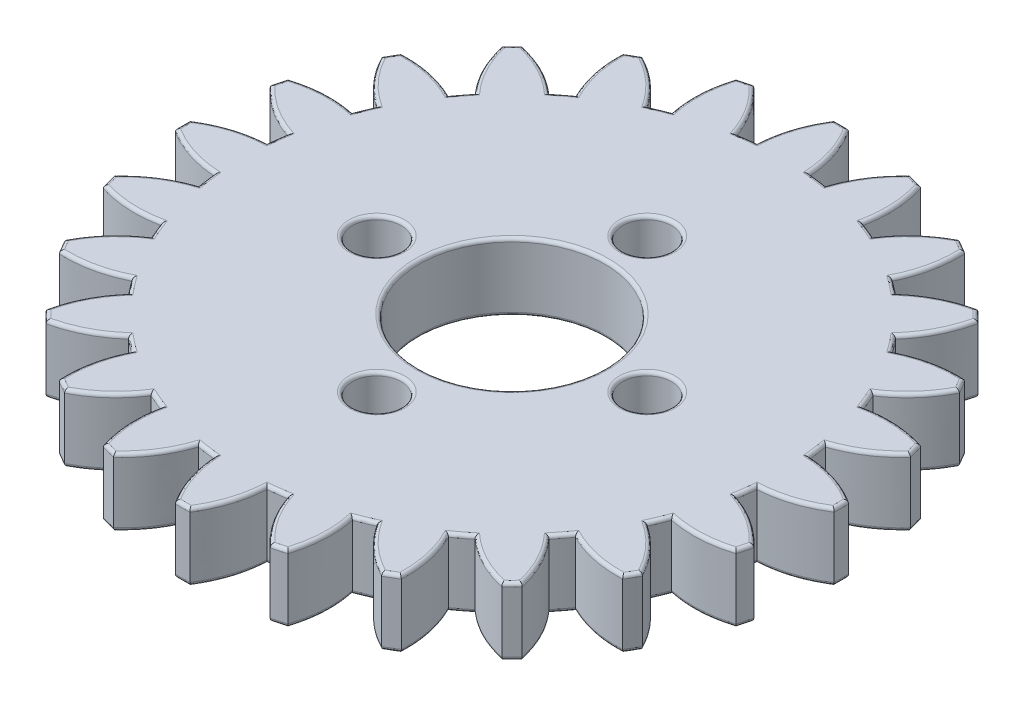
SolidWorks part; units mm, degrees
note: The reader was unsure of these and kept them because the rebuilt part matched: shared geometry of "스케치1<3>".
ref_plane "정면" through (0, 0, 0) normal (0, 0, 1) x (1, 0, 0)
ref_plane "윗면" through (0, 0, 0) normal (0, 1, 0) x (1, 0, 0)
ref_plane "우측면" through (0, 0, 0) normal (1, 0, 0) x (0, 0, -1)
sketch "스케치1" plane through (0, 0, 0) normal (0, 1, 0) x (1, 0, 0)
  line L0 (0, 0) -> (0, 19.5) construction
  line L1 (0, 0) -> (-7.8946, 0) construction
  line L2 (-0.4275, 0) -> (-0.4275, 19.4953) construction
  line L3 (-1.1775, 0) -> (-1.1775, 17.9614) construction
  line L4 (-1.5525, 0) -> (-1.5525, 16.0501) construction
  arc A0 (0.4275, 19.4953) -> (-0.4275, 19.4953) centre (0, 0) ccw
  circle A1 centre (0, 0) radius 16.125
  circle A2 centre (0, 0) radius 18 construction
  circle A3 centre (0, 0) radius 5.5
  spline S0 degree 2 poles (-0.4275, 19.4953) (-1.4409, 17.9243) (-1.5525, 16.0501) knots 0 0 0 1 1 1
  spline S1 degree 2 poles (0.4275, 19.4953) (1.4409, 17.9243) (1.5525, 16.0501) knots 0 0 0 1 1 1
  dimension "D1" = 36
  dimension "D2" = 1.5
  dimension "D3" = 1.875
  dimension "D7" = 11
  dimension "D4" = 0.375
  dimension "D5" = 0.75
  dimension "D6" = 1.1775
extrude "보스-돌출1" add sketch "스케치1" along normal blind 4 contours A1 A3
extrude "보스-돌출2" add sketch "스케치1<3>" along normal blind 4 contours S1 A0 S0 A1
sketch "스케치1<3>" plane through (0, 0, 0) normal (0, 1, 0) x (1, 0, 0) same geometry as "스케치1"
pattern_circular "원형 패턴1" count 24 over 360 about axis through (0, 4, 0) along (0, -1, 0) of "보스-돌출2"
sketch "스케치2" plane through (0, 4, 0) normal (0, 1, 0) x (1, 0, 0)
  circle A0 centre (0, 8) radius 1.45
  circle A1 centre (8, 0) radius 1.45
  circle A2 centre (0, -8) radius 1.45
  circle A3 centre (-8, 0) radius 1.45
  point P12 (0, 0)
  dimension "D2" = 2.9
  dimension "D1" = 8
  dimension "D3" = 4
extrude "컷-돌출1" cut sketch "스케치2" against normal through all contours A3
fillet "필렛1" radius 0.2 202 edges at (-12.7928, 0, 9.8163) (-12.7928, 4, 9.8163) (-16.8875, 0, 9.75) (-16.8875, 4, 9.75) (0, 0, -19.5) (-9.8163, 0, 12.7928) (-9.8163, 4, 12.7928) (-13.7886, 0, 13.7886) (-13.7886, 4, 13.7886) (0, 4, -19.5) (-6.1708, 0, 14.8976) (-6.1708, 4, 14.8976) (-9.75, 0, 16.8875) (-9.75, 4, 16.8875) (-2.1047, 0, 15.987) (-2.1047, 4, 15.987) (-5.047, 0, 18.8356) (-5.047, 4, 18.8356) (2.1047, 0, 15.987) (2.1047, 4, 15.987) (0, 0, 19.5) (0, 4, 19.5) (6.1708, 0, 14.8976) (6.1708, 4, 14.8976) (5.047, 0, 18.8356) (5.047, 4, 18.8356) (9.8163, 0, 12.7928) (9.8163, 4, 12.7928) (9.75, 0, 16.8875) (9.75, 4, 16.8875) (12.7928, 0, 9.8163) (12.7928, 4, 9.8163) (13.7886, 0, 13.7886) (13.7886, 4, 13.7886) (14.8976, 0, 6.1708) (14.8976, 4, 6.1708) (16.8875, 0, 9.75) (16.8875, 4, 9.75) (15.987, 0, 2.1047) (15.987, 4, 2.1047) (18.8356, 0, 5.047) (18.8356, 4, 5.047) (15.987, 0, -2.1047) (15.987, 4, -2.1047) (19.5, 0, 0) (19.5, 4, 0) (-6.1708, 0, -14.8976) (-6.1708, 4, -14.8976) (14.8976, 0, -6.1708) (14.8976, 4, -6.1708) (18.8356, 0, -5.047) (18.8356, 4, -5.047) (12.7928, 0, -9.8163) (12.7928, 4, -9.8163) (16.8875, 0, -9.75) (16.8875, 4, -9.75) (-5.047, 0, -18.8356) (9.8163, 0, -12.7928) (9.8163, 4, -12.7928) (13.7886, 0, -13.7886) (13.7886, 4, -13.7886) (-5.047, 4, -18.8356) (6.1708, 0, -14.8976) (6.1708, 4, -14.8976) (9.75, 0, -16.8875) (9.75, 4, -16.8875) (2.1047, 0, -15.987) (2.1047, 4, -15.987) (5.047, 0, -18.8356) (5.047, 4, -18.8356) (0, 0, -6.55) (0, 4, -6.55) (8, 0, 1.45) (8, 4, 1.45) (0, 0, 9.45) (0, 4, 9.45) (-8, 0, 1.45) (-8, 4, 1.45) (-9.8163, 0, -12.7928) (-9.8163, 4, -12.7928) (-9.75, 0, -16.8875) (-9.75, 4, -16.8875) (0, 0, 5.5) (-12.7928, 0, -9.8163) (-12.7928, 4, -9.8163) (-13.7886, 0, -13.7886) (-13.7886, 4, -13.7886) (-14.8976, 0, -6.1708) (-14.8976, 4, -6.1708) (-16.8875, 0, -9.75) (-16.8875, 4, -9.75) (-15.987, 0, -2.1047) (-15.987, 4, -2.1047) (0, 4, 5.5) (-18.8356, 0, -5.047) (-18.8356, 4, -5.047) (-15.987, 0, 2.1047) (-15.987, 4, 2.1047) (-19.5, 0, 0) (-19.5, 4, 0) (-2.1047, 0, -15.987) (-14.8976, 0, 6.1708) (-14.8976, 4, 6.1708) (-18.8356, 0, 5.047) (-2.1047, 4, -15.987) (-18.8356, 4, 5.047)
